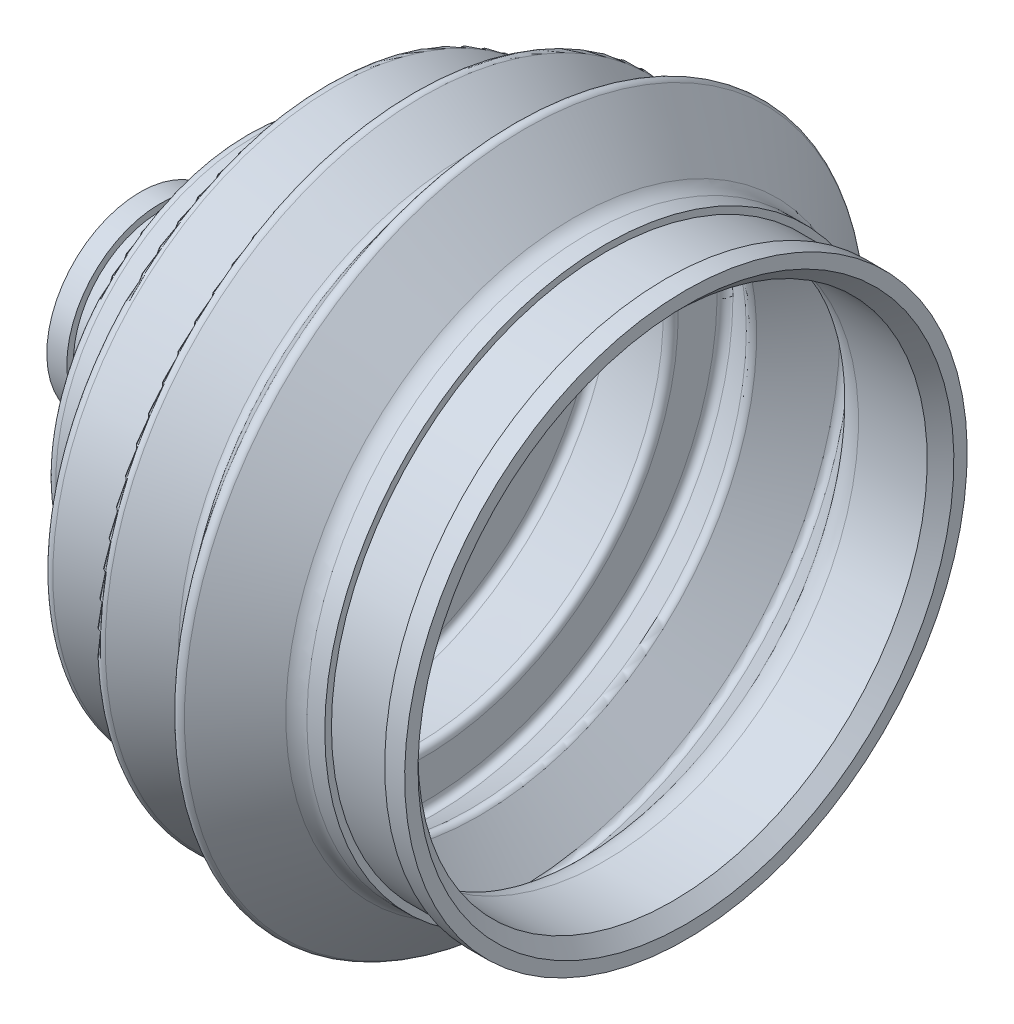
SolidWorks part; units mm, degrees
material "Резина"
ref_plane "Спереди" through (0, 0, 0) normal (0, 0, 1) x (1, 0, 0)
ref_plane "Сверху" through (0, 0, 0) normal (0, 1, 0) x (1, 0, 0)
ref_plane "Справа" through (0, 0, 0) normal (1, 0, 0) x (0, 0, -1)
sketch "Эскиз1" plane through (0, 0, 0) normal (0, 0, 1) x (1, 0, 0)
  line L0 (0, 0) -> (-186.3404, 0) construction
  line L1 (-82, 14) -> (-66, 14)
  line L2 (-66, 14) -> (-66, 30.25)
  line L3 (-66, 30.25) -> (-54, 27)
  line L4 (-54, 27) -> (-54, 42.75)
  line L5 (-54, 42.75) -> (-41, 39)
  line L6 (-41, 39) -> (-41, 48.75)
  line L7 (-41, 48.75) -> (-32, 43)
  line L8 (-32, 43) -> (-25, 52)
  line L9 (-25, 52) -> (-16, 42.25)
  line L10 (-16, 42.25) -> (0, 42.25)
  dimension "D1" = 60.5
  dimension "D2" = 85.5
  dimension "D3" = 97.5
  dimension "D4" = 104
  dimension "D5" = 16
  dimension "D6" = 12
  dimension "D7" = 13
  dimension "D8" = 16
  dimension "D9" = 16
  dimension "D10" = 28
  dimension "D11" = 84.5
  dimension "D12" = 16
  dimension "D13" = 54
  dimension "D14" = 78
  dimension "D15" = 86
  dimension "D16" = 82
  dimension "D17" = 7
revolve "Повернуть-Тонкостенный1" add sketch "Эскиз1" angle 360 about L0
sketch "Эскиз3" plane through (0, 0, 0) normal (0, 0, 1) x (1, 0, 0)
  line L0 (-82, 14) -> (-82, -14) construction
  line L1 (-82, 13) -> (-64.5, 13)
  line L2 (-82, 13) -> (-82, 10)
  line L3 (-82, 10) -> (-64.5, 10)
  line L4 (-64.5, 13) -> (-64.5, 10)
  line L5 (-64.5, -28.2897) -> (-64.5, 28.2897) construction
  line L6 (0, 0) -> (-106.3353, 0) construction
  line L7 (0, -42.25) -> (0, 42.25) construction
  line L8 (0, 41.25) -> (-16.6567, 41.25)
  line L9 (0, 41.25) -> (0, 38.25)
  line L10 (0, 38.25) -> (-16.6567, 38.25)
  line L11 (-16.6567, 41.25) -> (-16.6567, 38.25)
  line L12 (-16.6567, 40.75) -> (-16.6567, -40.75) construction
  dimension "D1" = 20
  dimension "D2" = 3
  dimension "D3" = 76.5
  dimension "D4" = 3
revolve "Повернуть1" add sketch "Эскиз3" angle 360 about L6
chamfer "Фаска1" distance 2 angle 45 1 edges at (0, 0, -38.25)
sketch "Эскиз4" plane through (0, 0, 0) normal (0, 0, 1) x (1, 0, 0)
  line L0 (0, 0) -> (-98.2661, 0) construction
  line L1 (-79, 18) -> (-70, 18)
  line L2 (-79, 18) -> (-79, 13)
  line L3 (-79, 13) -> (-70, 13)
  line L4 (-70, 18) -> (-70, 13)
  line L5 (-82, 14) -> (-82, -14) construction
  line L6 (0, -42.25) -> (0, 42.25) construction
  line L7 (-12, 46.25) -> (-3, 46.25)
  line L8 (-12, 46.25) -> (-12, 41.25)
  line L9 (-12, 41.25) -> (-3, 41.25)
  line L10 (-3, 46.25) -> (-3, 41.25)
  dimension "D1" = 26
  dimension "D2" = 9
  dimension "D3" = 3
  dimension "D4" = 5
  dimension "D5" = 82.5
  dimension "D6" = 9
  dimension "D7" = 3
  dimension "D8" = 5
revolve "Вырез-Повернуть1" cut sketch "Эскиз4" angle 360 about L0
fillet "Скругление1" radius 1 14 edges at (-64.5, 28.2897, 0) (-52.5, 25.0397, 0) (-52.5, 40.7561, 0) (-39.5, 37.0061, 0) (-39.5, 46.0117, 0) (-31.6554, 40.9998, 0) (-24.9022, 49.6825, 0) (-32, 43, 0) (-41, 39, 0) (-54, 27, 0) (-25, 52, 0) (-41, 48.75, 0) (-54, 42.75, 0) (-66, 30.25, 0)
fillet "Скругление2" radius 3 2 edges at (-66, 14, 0) (-16, 42.25, 0)
fillet "Скругление3" radius 5 2 edges at (-16.6567, 0, -38.25) (-64.5, 0, -10)
